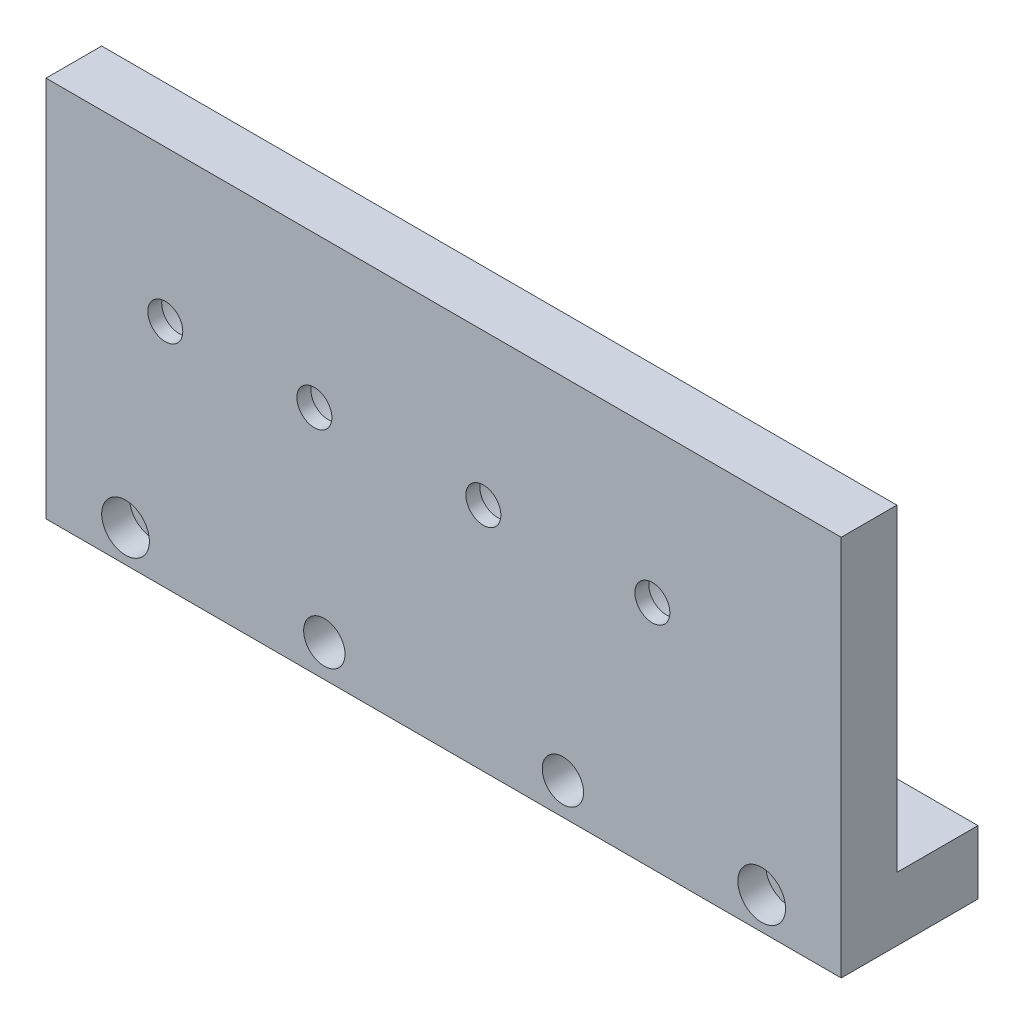
SolidWorks part; units mm, degrees
ref_plane "Front Plane" through (0, 0, 0) normal (0, 0, 1) x (1, 0, 0)
ref_plane "Top Plane" through (0, 0, 0) normal (0, 1, 0) x (1, 0, 0)
ref_plane "Right Plane" through (0, 0, 0) normal (1, 0, 0) x (0, 0, -1)
sketch "Sketch1" plane through (0, 0, 0) normal (0, 0, 1) x (1, 0, 0)
  line L1 (0, 0) -> (100, 0)
  line L2 (0, 0) -> (0, 48)
  line L3 (0, 48) -> (100, 48)
  line L4 (100, 0) -> (100, 48)
  dimension "D1" = 100
  dimension "D2" = 48
extrude "Boss-Extrude1" add sketch "Sketch1" along normal blind 7
sketch "Sketch2" plane through (0, 0, 7) normal (0, 0, 1) x (1, 0, 0)
  line L0 (0, 0) -> (100, 0) construction
  line L1 (0, 48) -> (0, 0) construction
  circle A0 centre (15, 29) radius 2.2
  circle A1 centre (33.75, 29) radius 2.2
  circle A2 centre (55, 29) radius 2.2
  circle A3 centre (76.25, 29) radius 2.2
  dimension "D1" = 4.4
  dimension "D2" = 18.75
  dimension "D3" = 21.25
  dimension "D4" = 21.25
  dimension "D5" = 29
  dimension "D6" = 15
extrude "Cut-Extrude1" cut sketch "Sketch2" against normal up to next
sketch "Sketch3" plane through (0, 0, 0) normal (0, 0, -1) x (-1, 0, 0)
  line L0 (0, 48) -> (0, 0) construction
  line L1 (-100, 0) -> (0, 0)
  line L2 (-100, 0) -> (-100, 8)
  line L3 (-100, 8) -> (0, 8)
  line L4 (0, 0) -> (0, 8)
  dimension "D1" = 8
extrude "Boss-Extrude2" add sketch "Sketch3" along normal blind 10.2
sketch "Sketch4" plane through (0, 0, 0) normal (0, 0, -1) x (-1, 0, 0)
  circle A0 centre (-76.25, 29) radius 6.6
  circle A1 centre (-55, 29) radius 6.6
  circle A2 centre (-33.75, 29) radius 6.6
  circle A3 centre (-15, 29) radius 6.6
  dimension "D1" = 13.2
extrude "Cut-Extrude2" cut sketch "Sketch4" against normal blind 5.25
sketch "Sketch5" plane through (0, 0, 7) normal (0, 0, 1) x (1, 0, 0)
  line L0 (35, 4.0521) -> (65, 4) construction
  line L1 (0, 0) -> (100, 0) construction
  circle A0 centre (35, 4.0521) radius 2.6
  circle A1 centre (65, 4) radius 2.6
  point P6 (50, 0)
  point P7 (50, 4.0261)
  dimension "D1" = 5.2
  dimension "D2" = 30
  dimension "D3" = 4
extrude "Cut-Extrude3" cut sketch "Sketch5" against normal blind 7
sketch "Sketch7" plane through (0, 0, 0) normal (0, 0, 1) x (1, 0, 0)
  circle A0 centre (35, 4.0521) radius 1.5
  circle A1 centre (65, 4) radius 1.5
  dimension "D1" = 3
extrude "Cut-Extrude4" cut sketch "Sketch7" against normal through all
sketch "Sketch8" plane through (0, 0, 7) normal (0, 0, 1) x (1, 0, 0)
  line L0 (10, 4.0521) -> (35, 4.0521) construction
  line L1 (0, 48) -> (0, 0) construction
  line L2 (100, 0) -> (100, 48) construction
  circle A0 centre (10, 4.0521) radius 1.7
  circle A1 centre (90, 4.0521) radius 1.7
  dimension "D1" = 3.4
  dimension "D2" = 10
  dimension "D3" = 10
extrude "Cut-Extrude5" cut sketch "Sketch8" against normal up to next
sketch "Sketch9" plane through (0, 0, 7) normal (0, 0, 1) x (1, 0, 0)
  circle A0 centre (10, 4.0521) radius 3
  circle A1 centre (90, 4.0521) radius 3
  dimension "D1" = 6
extrude "Cut-Extrude6" cut sketch "Sketch9" against normal blind 3.5
